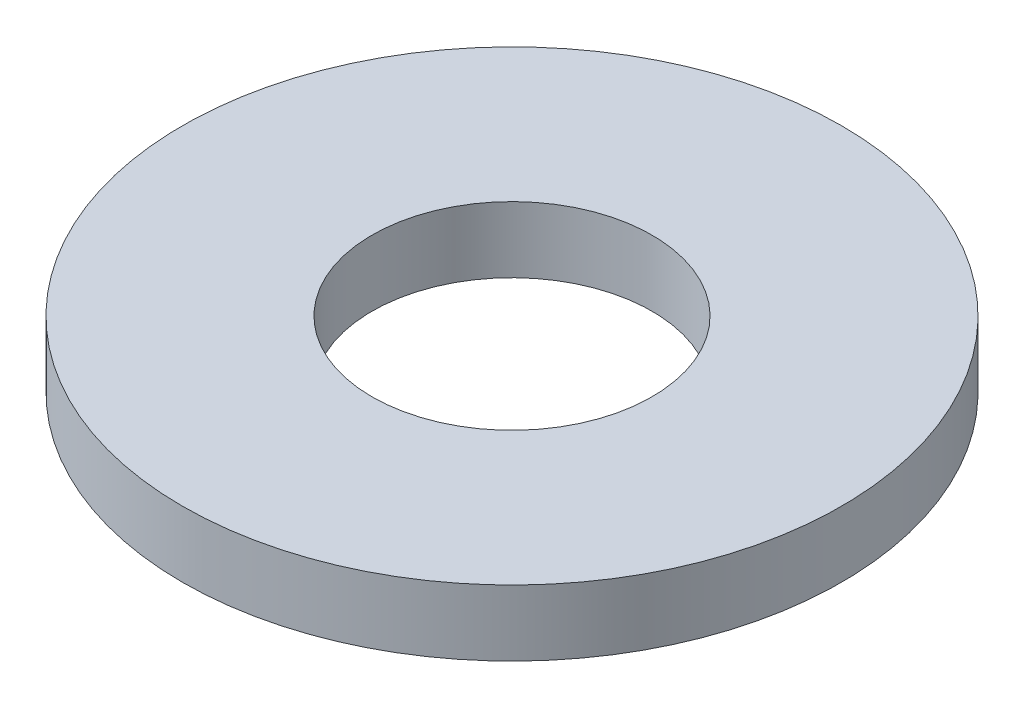
SolidWorks part; units mm, degrees
ref_plane "Front Plane" through (0, 0, 0) normal (0, 0, 1) x (1, 0, 0)
ref_plane "Top Plane" through (0, 0, 0) normal (0, 1, 0) x (1, 0, 0)
ref_plane "Right Plane" through (0, 0, 0) normal (1, 0, 0) x (0, 0, -1)
sketch "Sketch1" plane through (0, 0, 0) normal (0, 1, 0) x (1, 0, 0)
  line L1 (4, 0) -> (2, 3.4641) construction
  line L2 (2, 3.4641) -> (-2, 3.4641) construction
  line L3 (-2, 3.4641) -> (-4, 0) construction
  line L4 (-4, 0) -> (-2, -3.4641) construction
  line L5 (-2, -3.4641) -> (2, -3.4641) construction
  line L6 (2, -3.4641) -> (4, 0) construction
  circle A0 centre (0, 0) radius 3.4641 construction
  circle A1 centre (0, 0) radius 10
  circle A2 centre (0, 0) radius 4 construction
  circle A3 centre (0, 0) radius 4.25
  dimension "D1" = 8
  dimension "D2" = 20
  dimension "D3" = 8.5
extrude "Boss-Extrude1" add sketch "Sketch1" along normal blind 2
